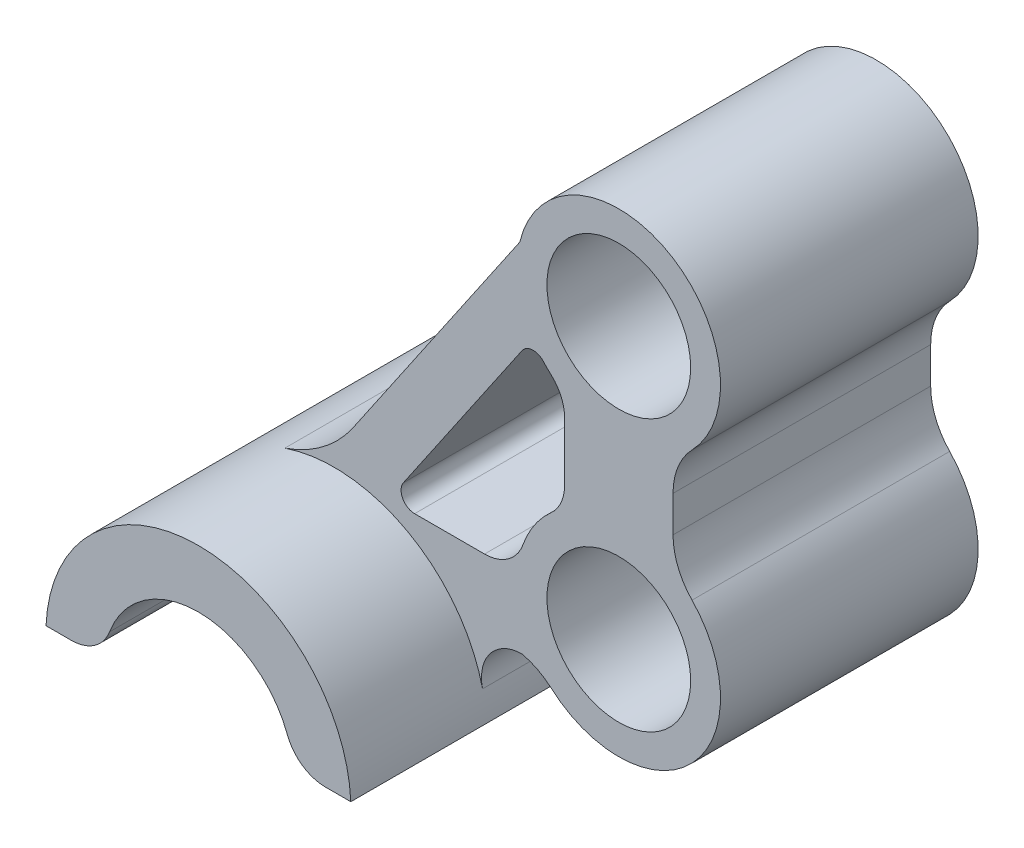
SolidWorks part; units mm, degrees
ref_plane "正面" through (0, 0, 0) normal (0, 0, 1) x (1, 0, 0)
ref_plane "平面" through (0, 0, 0) normal (0, 1, 0) x (1, 0, 0)
ref_plane "右側面" through (0, 0, 0) normal (1, 0, 0) x (0, 0, -1)
sketch "ｽｹｯﾁ1" plane through (0, 0, 0) normal (0, 0, 1) x (1, 0, 0)
  line L1 (4, 14.7) -> (-4, 14.7)
  line L2 (4, 14.7) -> (4, 5.3)
  line L3 (4, 5.3) -> (-4, 5.3)
  line L4 (-4, 14.7) -> (-4, 5.3)
  circle A0 centre (0, 20) radius 5.3
  circle A1 centre (0, 0) radius 5.3
  circle A2 centre (0, 20) radius 7.5
  circle A3 centre (0, 0) radius 7.5
  point P12 (0, 5.3)
  point P17 (0, 14.7)
  dimension "D1" = 0
  dimension "a" = 10.6
  dimension "D2" = 10.6
  dimension "D3" = 20
  dimension "D4" = 15
  dimension "D6" = 0
  dimension "D5" = 8
extrude "ﾎﾞｽ - 押し出し1" add sketch "ｽｹｯﾁ1" against normal blind 17 and the other way blind 2 contours L4 A3 L2 L3 A1 | L2 A3 L4 L3 | A3 L2 A2 L4 | L4 A2 L2 L1 | L2 A2 L4 L1 A0 region at (0, 13.7546, 0) region at (2, 14.9041, 0) region at (0, 10, 0) region at (6.3882, 3.5242, 0) region at (0, 6.2454, 0)
sketch "ｽｹｯﾁ3" plane through (0, 0, 2) normal (0, 0, 1) x (1, 0, 0)
  line L1 (-6, 0.5) -> (-21, 0.5)
  line L2 (-6, 0.5) -> (-6, -4.5)
  line L3 (-6, -4.5) -> (-21, -4.5)
  line L4 (-21, 0.5) -> (-21, -4.5)
  arc A1 (-4, 6.3443) -> (4, 6.3443) centre (0, 0) ccw construction
  dimension "D1" = 5
  dimension "D2" = 15
  dimension "６" = 6
extrude "ﾎﾞｽ - 押し出し3" add sketch "ｽｹｯﾁ3" against normal blind 19
sketch "ｽｹｯﾁ4" plane through (0, 0, 2) normal (0, 0, 1) x (1, 0, 0)
  line L0 (-21, 0.5) -> (-21, -4.5) construction
  line L1 (-32.25, -10.75) -> (-9.75, -10.75)
  line L2 (-21, -4.5) -> (-6, -4.5) construction
  line L3 (-7.4833, 0.5) -> (-21, 0.5) construction
  line L5 (-9.7611, -10.25) -> (-32.2389, -10.25)
  circle A0 centre (-21, -10.75) radius 7
  circle A1 centre (-21, -10.75) radius 11.25
  point P8 (-21, -10.75)
  line M6 (-21, 0.5) -> (-21, -4.5)
  line M7 (-21, -4.5) -> (-6, -4.5)
  dimension "D1" = 14
  dimension "D2" = 0
  dimension "D3" = 11.25
  dimension "D4" = 11.25
  dimension "D5" = 0.5
extrude "ﾎﾞｽ - 押し出し4" add sketch "ｽｹｯﾁ4" against normal blind 19 separate body contours L1 A1 A0 M7 | A1 L1 A0 M6 region at (-12.8881, -7.2084, 2) region at (-26.7982, -4.631, 2)
sketch "ｽｹｯﾁ5" plane through (0, 0, 2) normal (0, 0, 1) x (1, 0, 0)
  circle A0 centre (-21, -10.75) radius 7
extrude "ｶｯﾄ - 押し出し1" cut sketch "ｽｹｯﾁ5" against normal blind 19
sketch "ｽｹｯﾁ6" plane through (0, 0, 2) normal (0, 0, 1) x (1, 0, 0)
  line L0 (-9.7611, -10.25) -> (-32.2389, -10.25)
  circle A0 centre (-21, -10.75) radius 11.25
  circle A1 centre (-21, -10.75) radius 7
  arc M2 (-21, -3.75) -> (-17.8476, -4.5) centre (-21, -10.75) cw
  line M3 (-17.8476, -4.5) -> (-6, -4.5)
  line M10 (-21, 0.5) -> (-21, -3.75)
extrude "ﾎﾞｽ - 押し出し5" add sketch "ｽｹｯﾁ6" along normal blind 10 and the other way blind 29 contours A1 L0 A0 M3 | A0 M3 M10 M2 | A1 A0 L0 M10 region at (-12.8881, -7.2084, 2) region at (-17.2337, -2.3675, 2) region at (-26.7982, -4.631, 2)
fillet "ﾌｨﾚｯﾄ2" radius 3 1 edges at (-11.6459, -4.5, -7.5)
fillet "ﾌｨﾚｯﾄ3" radius 3 2 edges at (-27.9821, -10.25, -7.5) (-14.0179, -10.25, -7.5)
sketch "ｽｹｯﾁ7" plane through (0, 0, 2) normal (0, 0, 1) x (1, 0, 0)
  line L1 (5.7806, 16.0523) -> (-5.7806, 23.9477) construction
  line L2 (-5.7806, 23.9477) -> (-26.7806, -6.8023)
  line L3 (-26.7806, -6.8023) -> (-15.2194, -14.6977) construction
  line L4 (0, 20) -> (-21, -10.75) construction
  line L5 (-5.7806, 23.9477) -> (0, 20)
  line L6 (0, 20) -> (-21, -10.75)
  line L7 (-21, -10.75) -> (-26.7806, -6.8023)
  line L8 (-2.4774, 21.6919) -> (-23.4774, -9.0581)
  circle A0 centre (0, 20) radius 5.3 construction
  arc A2 (-14.4428, -8.3) -> (-27.5572, -8.3) centre (-21, -10.75) ccw construction
  circle A3 centre (0, 20) radius 7.5
  circle A4 centre (-21, -10.75) radius 11.25
  line M9 (-7.4833, 0.5) -> (-21, 0.5)
  arc M15 (4, 13.6557) -> (-4, 13.6557) centre (0, 20) ccw
  dimension "D1" = 0
  dimension "D2" = 0
  dimension "D3" = 7
  dimension "D4" = 3
extrude "ﾎﾞｽ - 押し出し6" add sketch "ｽｹｯﾁ7" against normal blind 19 contours L8 L2 M15 M9 region at (-13.3341, 9.5219, 2)
fillet "ﾌｨﾚｯﾄ4" radius 3 3 edges at (-7.4833, 0.5, -7.5) (-4, 6.3443, -7.5) (-4, 13.6557, -7.5)
fillet "ﾌｨﾚｯﾄ5" radius 1 2 edges at (-16.9499, 0.5, -7.5) (-6.354, 16.0154, -7.5)
fillet "ﾌｨﾚｯﾄ6" radius 5 3 edges at (-6, -4.5, -7.5) (4, 6.3443, -7.5) (4, 13.6557, -7.5)
fillet "ﾌｨﾚｯﾄ7" radius 10 1 edges at (-21.8138, 0.4705, -7.5)
